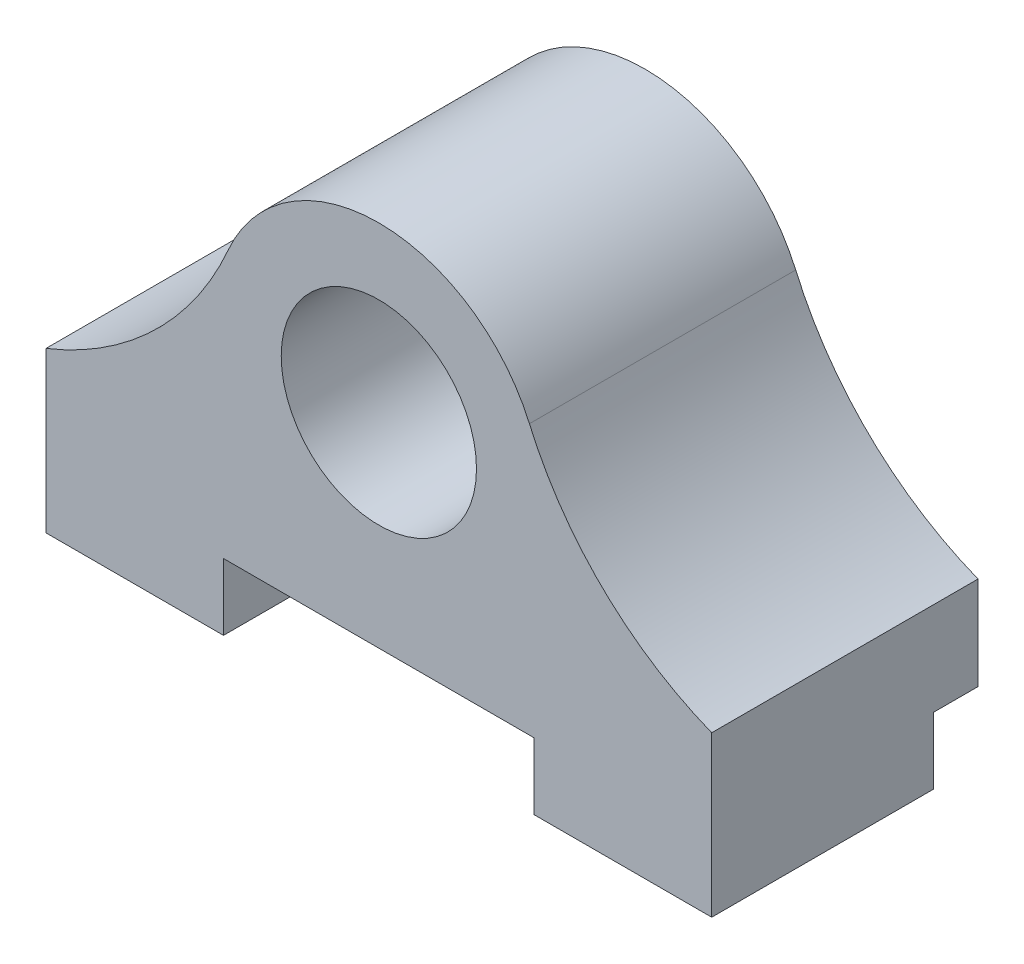
SolidWorks part; units mm, degrees
ref_plane "Front Plane" through (0, 0, 0) normal (0, 0, 1) x (1, 0, 0)
ref_plane "Top Plane" through (0, 0, 0) normal (0, 1, 0) x (1, 0, 0)
ref_plane "Right Plane" through (0, 0, 0) normal (1, 0, 0) x (0, 0, -1)
sketch "Sketch1" plane through (0, 0, 0) normal (0, 0, 1) x (1, 0, 0)
  line L0 (-15, -5) -> (15, -5)
  circle A0 centre (0, 0) radius 4.4
  arc A1 (-6.7851, 2.9534) -> (6.7851, 2.9534) centre (0, 0) cw
  arc A2 (6.7851, 2.9534) -> (15, -5) centre (20.5387, 8.94) ccw
  arc A3 (-6.7851, 2.9534) -> (-15, -5) centre (-20.5387, 8.94) cw
  point P12 (0, -5)
  dimension "D1" = 8.8
  dimension "D2" = 3
  dimension "D3" = 5
  dimension "D5" = 15
  dimension "D4" = 30
extrude "Boss-Extrude1" add sketch "Sketch1" along normal blind 10
extrude "Boss-Extrude2" add sketch "Sketch1<2>" against normal blind 2 contours A0 | A1 A3 L0 A2 A0 region at (-9.8792, -2.07, 0) region at (0, 0, 0)
sketch "Sketch1<2>" plane through (0, 0, 0) normal (0, 0, 1) x (1, 0, 0) same geometry as "Sketch1"
sketch "Sketch3" plane through (0, -5, 0) normal (0, -1, 0) x (1, 0, 0)
  line L1 (-15, 10) -> (15, 10)
  line L2 (-15, 10) -> (-15, -2)
  line L3 (-15, -2) -> (15, -2)
  line L4 (15, 10) -> (15, -2)
extrude "Boss-Extrude4" add sketch "Sketch3" along normal blind 7.2
sketch "Sketch2" plane through (0, 0, 0) normal (0, 1, 0) x (1, 0, 0)
  line L1 (-8, -8) -> (-15, -8)
  line L2 (-8, -8) -> (-8, 0)
  line L3 (-8, 0) -> (-15, 0)
  line L4 (-15, -8) -> (-15, 0)
  line L5 (-8, -8) -> (-15, 0) construction
  line L6 (-8, 0) -> (-15, -8) construction
  line L8 (8, -8) -> (15, -8)
  line L9 (8, -8) -> (8, 0)
  line L10 (8, 0) -> (15, 0)
  line L11 (15, -8) -> (15, 0)
  line L12 (8, -8) -> (15, 0) construction
  line L13 (8, 0) -> (15, -8) construction
  line L15 (-15, -10) -> (-15, 2) construction
  line L16 (15, -10) -> (15, 2) construction
  circle A0 centre (11.5, -4) radius 1.65
  circle A1 centre (-11.5, -4) radius 1.65
  point P0 (-11.5, -4)
  point P7 (11.5, -4)
  point P12 (15, -4)
  dimension "D3" = 3.3
  dimension "D1" = 8
  dimension "D2" = 7
extrude "Cut-Extrude2" cut sketch "Sketch2" along normal blind 8 from surface contours A1 | A0 region at (-11.5, 0, 4) starting at face at (0, -12.2, 4)
sketch "Sketch5" plane through (0, 0, -2) normal (0, 0, -1) x (-1, 0, 0)
  line L0 (-15, -12.2) -> (-15, -5) construction
  line L1 (-15, -12.2) -> (15, -12.2)
  line L2 (-15, -12.2) -> (-15, -9.2)
  line L3 (-15, -9.2) -> (15, -9.2)
  line L4 (15, -12.2) -> (15, -9.2)
  line L5 (15, -12.2) -> (15, -5) construction
  line L6 (-2.5, -12.2) -> (-15, -12.2) construction
  dimension "D1" = 3
extrude "Cut-Extrude3" cut sketch "Sketch5" against normal blind 2 and the other way through all
sketch "Sketch6" plane through (0, 0, 10) normal (0, 0, 1) x (1, 0, 0)
  line L0 (15, -12.2) -> (-15, -12.2) construction
  line L1 (-7, -12.2) -> (7, -12.2)
  line L2 (-7, -12.2) -> (-7, -9.2)
  line L3 (-7, -9.2) -> (7, -9.2)
  line L4 (7, -12.2) -> (7, -9.2)
  line L5 (-7, -12.2) -> (7, -9.2) construction
  line L6 (-7, -9.2) -> (7, -12.2) construction
  point P0 (0, -10.7)
  point P7 (0, 0)
  dimension "D1" = 3
  dimension "D2" = 14
extrude "Cut-Extrude4" cut sketch "Sketch6" against normal through all both and the other way through all
